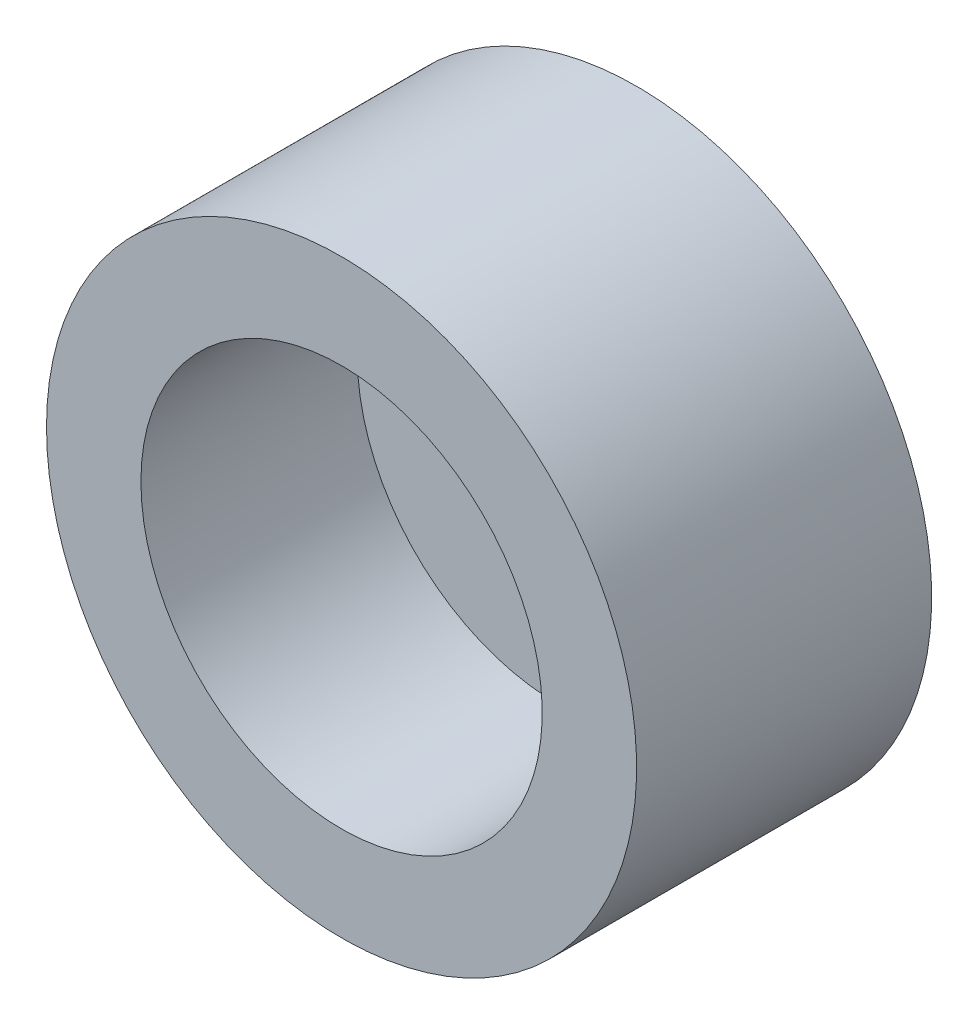
SolidWorks part; units mm, degrees
ref_plane "Front" through (0, 0, 0) normal (0, 0, 1) x (1, 0, 0)
ref_plane "Top" through (0, 0, 0) normal (0, 1, 0) x (1, 0, 0)
ref_plane "Right" through (0, 0, 0) normal (1, 0, 0) x (0, 0, -1)
sketch "Sketch1" plane through (0, 0, 0) normal (0, 0, 1) x (1, 0, 0)
  circle A0 centre (0, 0) radius 12.954
  circle A1 centre (0, 0) radius 19.05
  dimension "D1" = 25.908
  dimension "D2" = 38.1
extrude "Boss-Extrude1" add sketch "Sketch1" along normal blind 19.05
extrude "Boss-Extrude2" add sketch "Sketch1<2>" along normal blind 5.08 contours A0 region at (0, 0, 0)
sketch "Sketch1<2>" plane through (0, 0, 0) normal (0, 0, 1) x (1, 0, 0) same geometry as "Sketch1"
